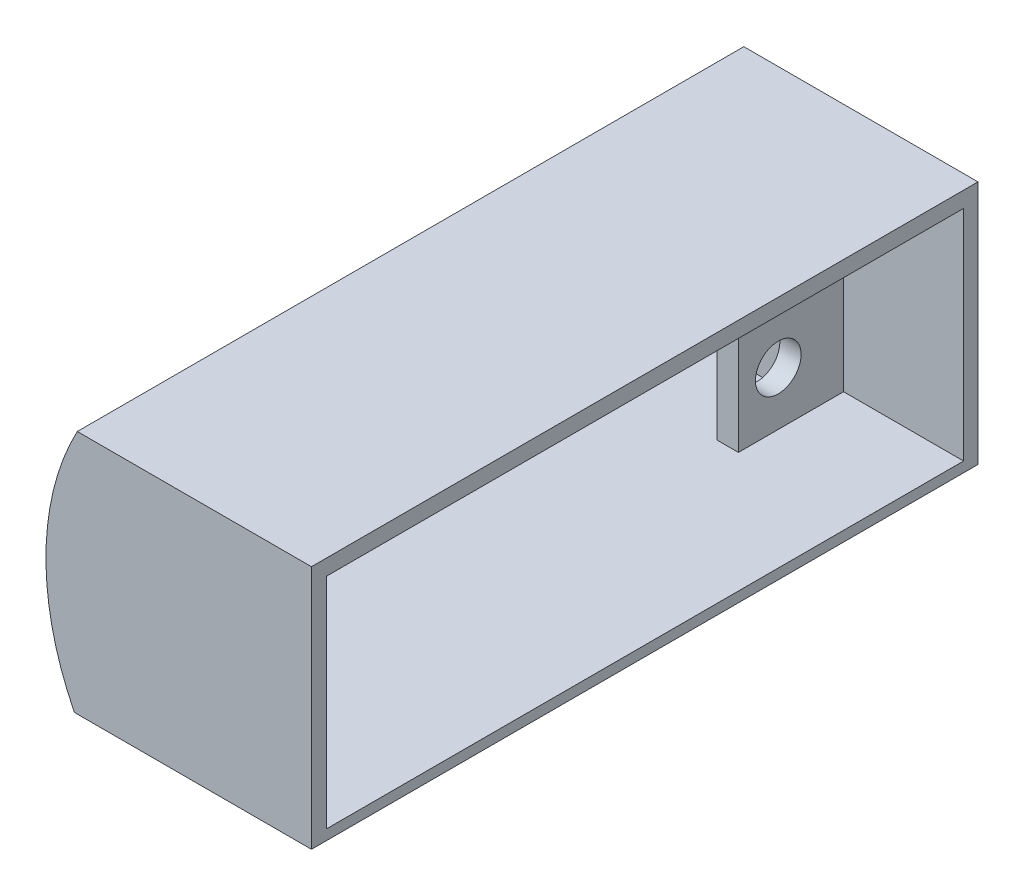
SolidWorks part; units mm, degrees
material "Custom Plastic"
ref_plane "Front Plane" through (0, 0, 0) normal (0, 0, 1) x (1, 0, 0)
ref_plane "Top Plane" through (0, 0, 0) normal (0, 1, 0) x (1, 0, 0)
ref_plane "Right Plane" through (0, 0, 0) normal (1, 0, 0) x (0, 0, -1)
sketch "Sketch1" plane through (0, 0, 0) normal (0, 0, 1) x (1, 0, 0)
  line L0 (-13.75, 13.75) -> (13.75, -13.75) construction
  line L1 (-13.75, 13.75) -> (13.75, 13.75)
  line L2 (-13.75, 13.75) -> (-13.75, -13.75)
  line L3 (-13.75, -13.75) -> (13.75, -13.75)
  line L4 (13.75, 13.75) -> (13.75, -13.75)
  circle A0 centre (0, 0) radius 25
  point P7 (0, 0)
  dimension "D2" = 50
  dimension "2.75" = 27.5
extrude "Boss-Extrude1" add sketch "Sketch1" along normal blind 55
sketch "Sketch2" plane through (0, 0, 0) normal (0, 0, -1) x (-1, 0, 0)
  circle A0 centre (0, 0) radius 25
  circle A1 centre (0, 0) radius 25
  circle A2 centre (0, 0) radius 25
  circle M2 centre (0, 0) radius 25
  line M3 (13.75, 13.75) -> (13.75, -13.75)
  line M4 (13.75, -13.75) -> (-13.75, -13.75)
  line M5 (-13.75, -13.75) -> (-13.75, 13.75)
  line M6 (-13.75, 13.75) -> (13.75, 13.75)
  dimension "D1" = 0
extrude "Boss-Extrude2" add sketch "Sketch2" along normal blind 5 contours M2 M6 M3 M4 M5 | M3 M6 M5 M4 region at (24.2929, 0, 0) region at (0, 0, 0)
sketch "Sketch3" plane through (0, 0, -5) normal (0, 0, -1) x (-1, 0, 0)
  line L1 (0, 25) -> (25, 25)
  line L2 (0, 25) -> (0, -25)
  line L3 (0, -25) -> (25, -25)
  line L4 (25, 25) -> (25, -25)
  circle A0 centre (0, 0) radius 25 construction
extrude "Boss-Extrude3" add sketch "Sketch3" along normal blind 80
ref_plane "Plane1" through (0, 0, -5) normal (0, 0, 1) x (1, 0, 0)
fillet "Fillet1" radius 2.5 4 edges at (-13.75, 13.75, 27.5) (13.75, 13.75, 27.5) (-13.75, -13.75, 27.5) (13.75, -13.75, 27.5)
fillet "Fillet2" radius 2.5 1 edges at (13.75, 0, 55) type face fillet first side face at (25, 0, 55) second side face at (13.75, 0, 27.5) tangent propagation no
ref_plane "Plane2" through (-50, 0, 0) normal (-1, 0, 0) x (0, 0, 1)
sketch "Sketch18" plane through (0, 0, -5) normal (0, 0, 1) x (1, 0, 0)
  line L0 (0, -25) -> (-25, -25)
  line L1 (-25, 0) -> (-25, 25)
  line L2 (-25, -25) -> (0, -25)
  line L3 (-25, 0) -> (-25, -25)
  line L4 (-25, -25) -> (0, -25)
  line L5 (-25, 0) -> (-25, -25)
  line L6 (-25, 25) -> (0, 25)
  arc A1 (-25, 0) -> (0, -25) centre (0, 0) ccw
  arc A2 (-25, 0) -> (0, -25) centre (0, 0) ccw
  circle A3 centre (0, 0) radius 25
  circle A4 centre (0, 0) radius 25
  line M5 (-25, 25) -> (-25, 0)
  arc M6 (-25, 0) -> (0, 25) centre (0, 0) cw
  line M7 (0, 25) -> (-25, 25)
  dimension "D1" = 0
  dimension "D2" = 0
sketch "Sketch21" plane through (0, 0, 0) normal (1, 0, 0) x (0, 0, -1)
  line L0 (22, 10.3) -> (82, 10.3)
  line L1 (82, 10.3) -> (82, -10.3)
  line L2 (82, -10.3) -> (22, -10.3)
  line L3 (22, -10.3) -> (22, 10.3)
  line L6 (85, 25) -> (85, -25) construction
  line L7 (52, -10.3) -> (52, -25)
  line L8 (85, -25) -> (5, -25) construction
  line L9 (52, 10.3) -> (52, 25)
  line L10 (85, 25) -> (5, 25) construction
  dimension "D1" = 3
  dimension "D2" = 60
  dimension "D3" = 20.6
extrude "Cut-Extrude1" cut sketch "Sketch21" against normal blind 11.3 contours L3 L0 L1 L2
sketch "Sketch22" plane through (0, 0, 0) normal (1, 0, 0) x (0, 0, -1)
  line L0 (31.6, 10.3) -> (72.1, 10.3)
  line L1 (22, 10.3) -> (82, 10.3) construction
  line L2 (72.1, 10.3) -> (72.1, -10.3)
  line L4 (72.1, -10.3) -> (31.6, -10.3)
  line L5 (31.6, 10.3) -> (31.6, -10.3)
  line L6 (85, 25) -> (85, -25) construction
  line M9 (82, -10.3) -> (22, -10.3)
  line M11 (22, 10.3) -> (82, 10.3)
  dimension "D1" = 40.5
  dimension "D2" = 12.9
  dimension "D3" = 20.6
extrude "Cut-Extrude2" cut sketch "Sketch22" against normal through all contours L5 L2 M11 M9 region at (0, 0, -51.85)
extrude "Cut-Extrude3" cut sketch "Sketch18" against normal through all contours A2 L5 L0 | M7 M5 M6 region at (-19.4158, -19.4158, -5) region at (-19.4158, 19.4158, -5)
sketch "Sketch23" plane through (0, 0, 0) normal (1, 0, 0) x (0, 0, -1)
  line L0 (27.85, 5.25) -> (27.85, -5.25) construction
  line L1 (27.85, -5.25) -> (75.85, -5.25) construction
  line L2 (75.85, -5.25) -> (75.85, 5.25) construction
  line L3 (75.85, 5.25) -> (27.85, 5.25) construction
  circle A0 centre (75.85, 5.25) radius 2.15
  circle A1 centre (75.85, -5.25) radius 2.15
  circle A3 centre (27.85, 5.25) radius 2.15
  circle A4 centre (27.85, -5.25) radius 2.15
  dimension "D1" = 4.3
extrude "Cut-Extrude4" cut sketch "Sketch23" against normal through all contours A4 | A0 | A1 | A3 region at (0, 5.25, -75.85) region at (0, -5.25, -75.85) region at (0, -5.25, -27.85)
ref_plane "Plane3" through (0, 0, -51.85) normal (0, 0, -1) x (-1, 0, 0)
sketch "Sketch24" plane through (0, 0, -51.85) normal (0, 0, -1) x (-1, 0, 0)
  line L6 (13.3, 10.3) -> (13.3, -10.3)
  line L16 (22.7796, 10.3) -> (11.3, 10.3)
  line L17 (11.3, 10.3) -> (11.3, -10.3)
  line L18 (11.3, -10.3) -> (22.7796, -10.3)
  line L19 (22.7796, 10.3) -> (11.3, 10.3)
  line L20 (11.3, 10.3) -> (11.3, -10.3)
  line L21 (11.3, -10.3) -> (22.7796, -10.3)
  line L24 (0, 10.3) -> (0, -10.3)
  line L25 (0, -10.3) -> (11.3, -10.3)
  line L26 (11.3, -10.3) -> (11.3, 10.3)
  line L27 (11.3, 10.3) -> (0, 10.3)
  line L30 (11.3, -10.3) -> (11.3, 10.3)
  arc A1 (22.7796, -10.3) -> (22.7796, 10.3) centre (0, 0) ccw
  arc A5 (22.7796, -10.3) -> (22.7796, 10.3) centre (0, 0) ccw
  dimension "D1" = 0
  dimension "D2" = 2
  dimension "D4" = 20.6
  dimension "D3" = 0
extrude "Cut-Extrude7" cut sketch "Sketch24" against normal mid plane 55 contours L21 A5 L19 L6 region at (-18.8065, 0, -51.85)
sketch "Sketch25" plane through (0, 0, 0) normal (1, 0, 0) x (0, 0, -1)
  line L0 (85, -25) -> (5, -25) construction
  line L1 (-55, 25) -> (20.5988, 25)
  line L2 (-55, 25) -> (-55, -25)
  line L3 (-55, -25) -> (20.5988, -25)
  line L4 (20.5988, 25) -> (20.5988, -25)
  line L6 (20.5988, -11.2627) -> (83.3573, -11.2627)
  line L7 (20.5988, -11.2627) -> (20.5988, -25)
  line L8 (20.5988, -25) -> (85, -25)
  line L9 (85, -11.2627) -> (85, -25)
  line L10 (20.5988, 11.7835) -> (83.3573, 11.7835)
  line L11 (20.5988, 11.7835) -> (20.5988, 25)
  line L12 (20.5988, 25) -> (85, 25)
  line L13 (85, 11.7835) -> (85, 25)
  line L15 (85, -11.2627) -> (85, 11.7835)
  line L17 (83.3573, -11.2627) -> (83.3573, 11.7835)
  line M11 (5, -25) -> (85, -25)
  line M12 (85, -25) -> (85, 25)
extrude "Cut-Extrude9" cut sketch "Sketch25" against normal through all contours L6 L4 M11 M12 | L17 L10 L11 L12 L13 L15 L9 L8 L7 L6 region at (0, 24.1847, -52.7994)
sketch "Sketch26" plane through (0, 0, 0) normal (1, 0, 0) x (0, 0, -1)
  line L1 (-55, 25) -> (20.5988, 25)
  line L2 (-55, 25) -> (-55, -25)
  line L3 (-55, -25) -> (20.5988, -25)
  line L4 (20.5988, 25) -> (20.5988, -25)
extrude "Cut-Extrude10" cut sketch "Sketch26" against normal through all both and the other way through all contours L2 L1 L4 L3
